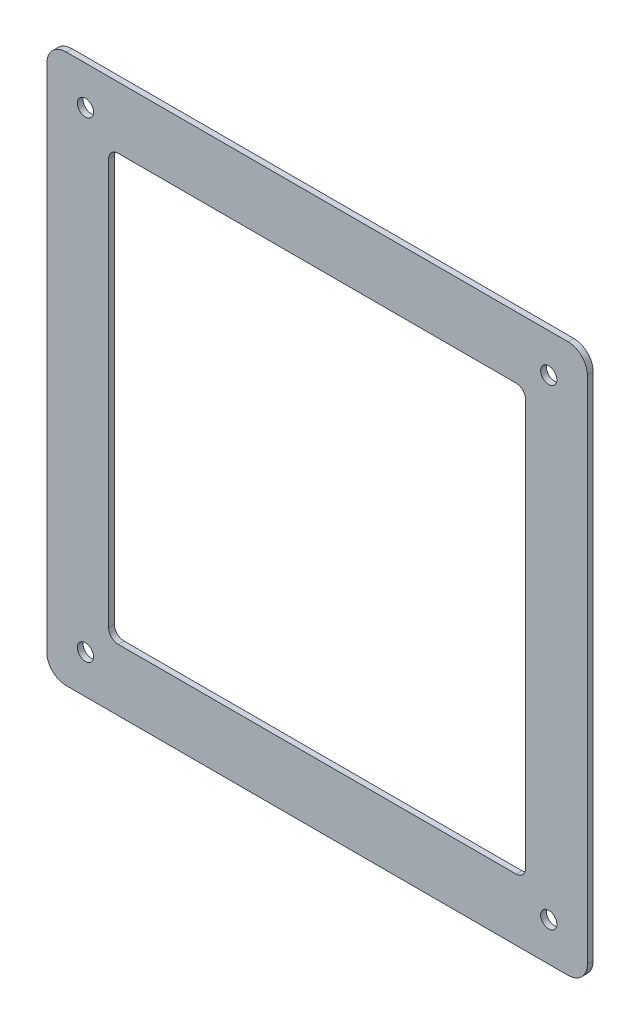
SolidWorks part; units mm, degrees
material "天然橡胶"
ref_plane "前视基准面" through (0, 0, 0) normal (0, 0, 1) x (1, 0, 0)
ref_plane "上视基准面" through (0, 0, 0) normal (0, 1, 0) x (1, 0, 0)
ref_plane "右视基准面" through (0, 0, 0) normal (1, 0, 0) x (0, 0, -1)
sketch "草图1" plane through (0, 0, 0) normal (0, 0, 1) x (1, 0, 0)
  line L1 (-108, -110.125) -> (108, -110.125)
  line L2 (-108, -110.125) -> (-108, 110.125)
  line L3 (-108, 110.125) -> (108, 110.125)
  line L4 (108, -110.125) -> (108, 110.125)
  line L5 (-108, -110.125) -> (108, 110.125) construction
  line L6 (-108, 110.125) -> (108, -110.125) construction
  line L7 (-140, -142.125) -> (140, -142.125)
  line L8 (-140, -142.125) -> (-140, 142.125)
  line L9 (-140, 142.125) -> (140, 142.125)
  line L10 (140, -142.125) -> (140, 142.125)
  line L11 (-140, -142.125) -> (140, 142.125) construction
  line L12 (-140, 142.125) -> (140, -142.125) construction
  point P0 (0, 0)
  point P6 (0, 0)
  dimension "D1" = 216
  dimension "D2" = 220.25
  dimension "D3" = 32
  dimension "D4" = 32
extrude "凸台-拉伸1" add sketch "草图1" along normal blind 3
fillet "圆角1" radius 10 4 edges at (140, 142.125, 1.5) (140, -142.125, 1.5) (-140, -142.125, 1.5) (-140, 142.125, 1.5)
fillet "圆角2" radius 5 4 edges at (-108, 110.125, 1.5) (-108, -110.125, 1.5) (108, -110.125, 1.5) (108, 110.125, 1.5)
hole_wizard "Ø8.4 (8.4) 直径孔1" positions "草图2" profile "草图3" hole size "Ø8.4" standard "GB" end condition through all
sketch "草图2" plane through (0, 0, 3) normal (0, 0, 1) x (1, 0, 0)
  line L0 (-140, 132.125) -> (-140, -132.125) construction
  line L1 (130, 142.125) -> (-130, 142.125) construction
  line L2 (140, -132.125) -> (140, 132.125) construction
  line L3 (-130, -142.125) -> (130, -142.125) construction
  point P0 (120, -122.125)
  point P3 (-120, 122.125)
  point P6 (-120, -122.125)
  point P9 (120, 122.125)
  dimension "D1" = 20
  dimension "D2" = 20
  dimension "D3" = 20
  dimension "D4" = 20
  dimension "D5" = 20
  dimension "D6" = 20
  dimension "D7" = 20
  dimension "D8" = 20
sketch "草图3" plane through (120, -122.125, 3) normal (1, 0, 0) x (0, -1, 0)
  line L0 (0, 0) -> (0, 3)
  line L1 (0, 3) -> (4.2, 3)
  line L2 (4.2, 3) -> (4.2, 0)
  line L5 (4.2, 0) -> (0, 0)
  line L11 (0, -6.35) -> (0, 107.95) construction
  dimension "通孔孔直径" = 8.4
  dimension "通孔孔深度" = 3
